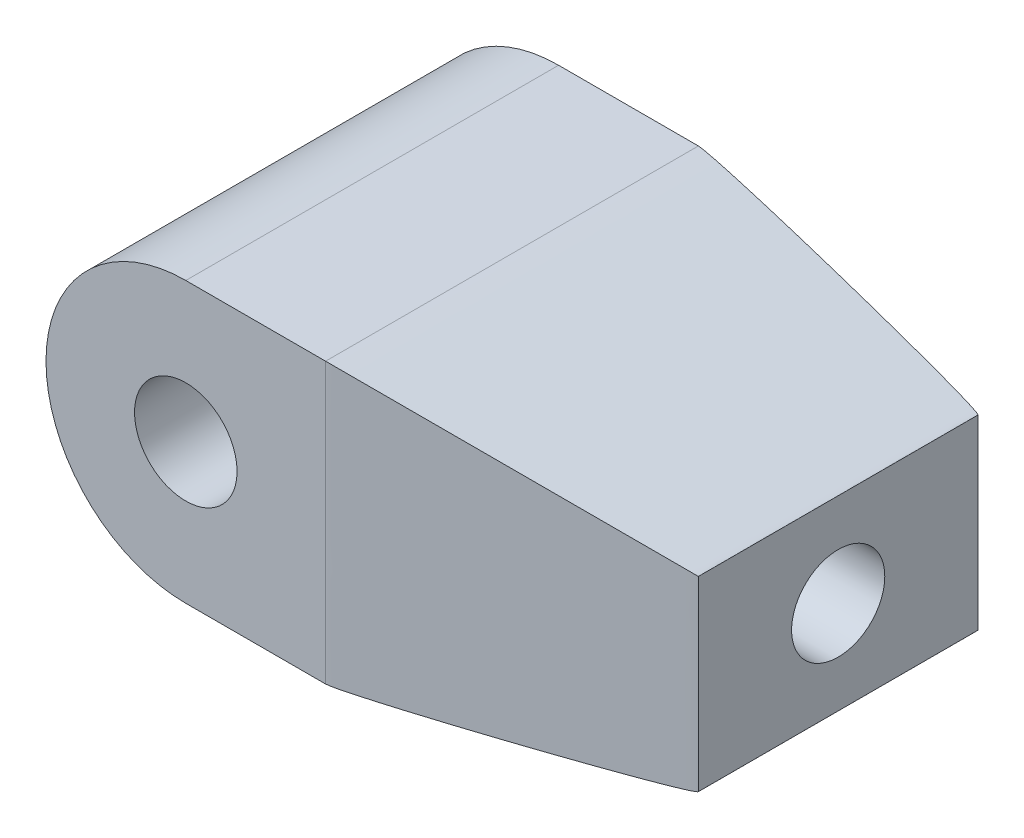
SolidWorks part; units mm, degrees
ref_plane "前视基准面" through (0, 0, 0) normal (0, 0, 1) x (1, 0, 0)
ref_plane "上视基准面" through (0, 0, 0) normal (0, 1, 0) x (1, 0, 0)
ref_plane "右视基准面" through (0, 0, 0) normal (1, 0, 0) x (0, 0, -1)
sketch "草图1" plane through (0, 0, 0) normal (0, 1, 0) x (1, 0, 0)
  line L1 (0, 0) -> (13, 0)
  line L2 (0, 0) -> (0, 8)
  line L3 (0, 8) -> (13, 8)
  line L4 (13, 0) -> (13, 8)
  dimension "D1" = 8
  dimension "D2" = 13
extrude "凸台-拉伸1" add sketch "草图1" along normal blind 6
sketch "草图2" plane through (0, 0, 0) normal (0, 0, 1) x (1, 0, 0)
  line L0 (0, 6) -> (0, 0) construction
  line L1 (0, 0) -> (13, 0) construction
  circle A0 centre (3, 3) radius 1.1
  point P4 (0, 3)
  dimension "D1" = 2.2
  dimension "D2" = 3
  dimension "D3" = 3
extrude "切除-拉伸1" cut sketch "草图2" against normal through all
sketch "草图3" plane through (13, 0, 0) normal (1, 0, 0) x (0, 0, -1)
  circle A0 centre (4, 3) radius 1
  dimension "D1" = 2
extrude "切除-拉伸2" cut sketch "草图3" against normal blind 8
fillet "圆角1" radius 1 4 edges at (13, 3, -8) (13, 0, -4) (13, 3, 0) (13, 6, -4) second distance 7 conic rho 0.05 first distance on face at (13, 3, -5)
fillet "圆角2" radius 3 2 edges at (0, 0, -4) (0, 6, -4)
